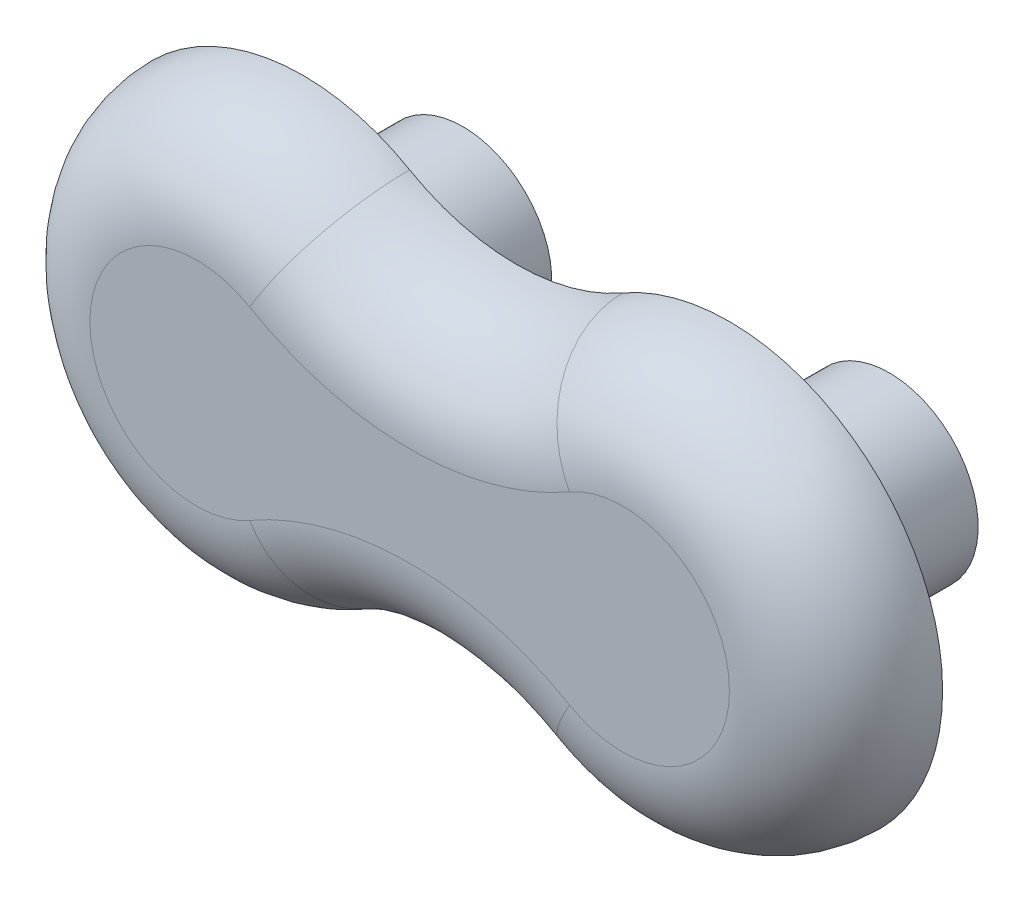
SolidWorks part; units mm, degrees
ref_plane "Спереди" through (0, 0, 0) normal (0, 0, 1) x (1, 0, 0)
ref_plane "Сверху" through (0, 0, 0) normal (0, 1, 0) x (1, 0, 0)
ref_plane "Справа" through (0, 0, 0) normal (1, 0, 0) x (0, 0, -1)
sketch "Эскиз2" plane through (0, 0, 0) normal (0, 0, 1) x (1, 0, 0)
  arc A7 (9, 5.1962) -> (9, -5.1962) centre (6, 0) ccw
  arc A8 (15, -5.1962) -> (15, 5.1962) centre (18, 0) ccw
  arc A9 (9, 5.1962) -> (15, 5.1962) centre (12, 10.3923) ccw
  arc A10 (15, -5.1962) -> (9, -5.1962) centre (12, -10.3923) ccw
extrude "Бобышка-Вытянуть1" add sketch "Эскиз2" along normal blind 3 from offset 4.5
sketch "Эскиз3" plane through (0, 0, 4.5) normal (0, 0, -1) x (-1, 0, 0)
  circle A0 centre (-18, 0) radius 2.5
  circle A1 centre (-6, 0) radius 2.5
extrude "Бобышка-Вытянуть2" add sketch "Эскиз3" along normal blind 4.5
sketch "Эскиз6" plane through (0, 0, 4.5) normal (0, 0, -1) x (-1, 0, 0)
  circle A3 centre (-18, 0) radius 3
  circle A4 centre (-6, 0) radius 3
extrude "Бобышка-Вытянуть3" add sketch "Эскиз6" along normal blind 0.5
fillet "Скругление1" radius 3 4 edges at (0, 0, 7.5) (12, 4.3923, 7.5) (24, 0, 7.5) (12, -4.3923, 7.5)
